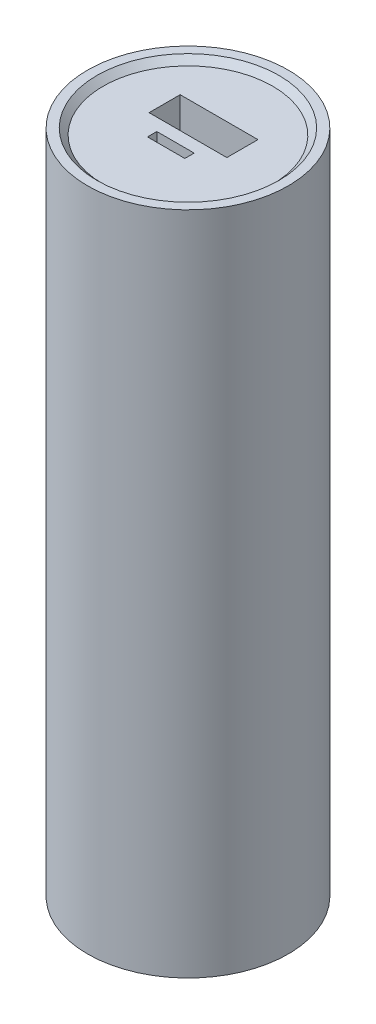
SolidWorks part; units mm, degrees
ref_plane "Front Plane" through (0, 0, 0) normal (0, 0, 1) x (1, 0, 0)
ref_plane "Top Plane" through (0, 0, 0) normal (0, 1, 0) x (1, 0, 0)
ref_plane "Right Plane" through (0, 0, 0) normal (1, 0, 0) x (0, 0, -1)
sketch "Sketch1" plane through (0, 0, 0) normal (0, 1, 0) x (1, 0, 0)
  circle A0 centre (0, 0) radius 16.125
  dimension "D1" = 32.25
extrude "Boss-Extrude1" add sketch "Sketch1" along normal blind 106.9
sketch "Sketch2" plane through (0, 106.9, 0) normal (0, 1, 0) x (1, 0, 0)
  circle A0 centre (0, 0) radius 14.625
  circle A1 centre (0, 0) radius 16.125 construction
  dimension "D1" = 1.5
extrude "Cut-Extrude1" cut sketch "Sketch2" against normal blind 1
chamfer "Chamfer1" distance 1 angle 45 1 edges at (0, 105.9, 14.625)
sketch "Sketch3" plane through (0, 105.9, 0) normal (0, 1, 0) x (1, 0, 0)
  line L1 (6.25, 0) -> (-6.25, 0)
  line L2 (6.25, 0) -> (6.25, 5)
  line L3 (6.25, 5) -> (-6.25, 5)
  line L4 (-6.25, 0) -> (-6.25, 5)
  line L5 (6.25, 0) -> (-6.25, 5) construction
  line L6 (6.25, 5) -> (-6.25, 0) construction
  line L7 (3, -3.5) -> (-3, -3.5)
  line L8 (3, -3.5) -> (3, -2)
  line L9 (3, -2) -> (-3, -2)
  line L10 (-3, -3.5) -> (-3, -2)
  line L11 (3, -3.5) -> (-3, -2) construction
  line L12 (3, -2) -> (-3, -3.5) construction
  point P0 (0, 2.5)
  point P5 (0, -2.75)
  point P10 (0, 0)
  point P12 (0, -3.8705)
  dimension "D1" = 5
  dimension "D2" = 12.5
  dimension "D3" = 1.5
  dimension "D4" = 6
  dimension "D5" = 2
extrude "Cut-Extrude2" cut sketch "Sketch3" against normal blind 5
